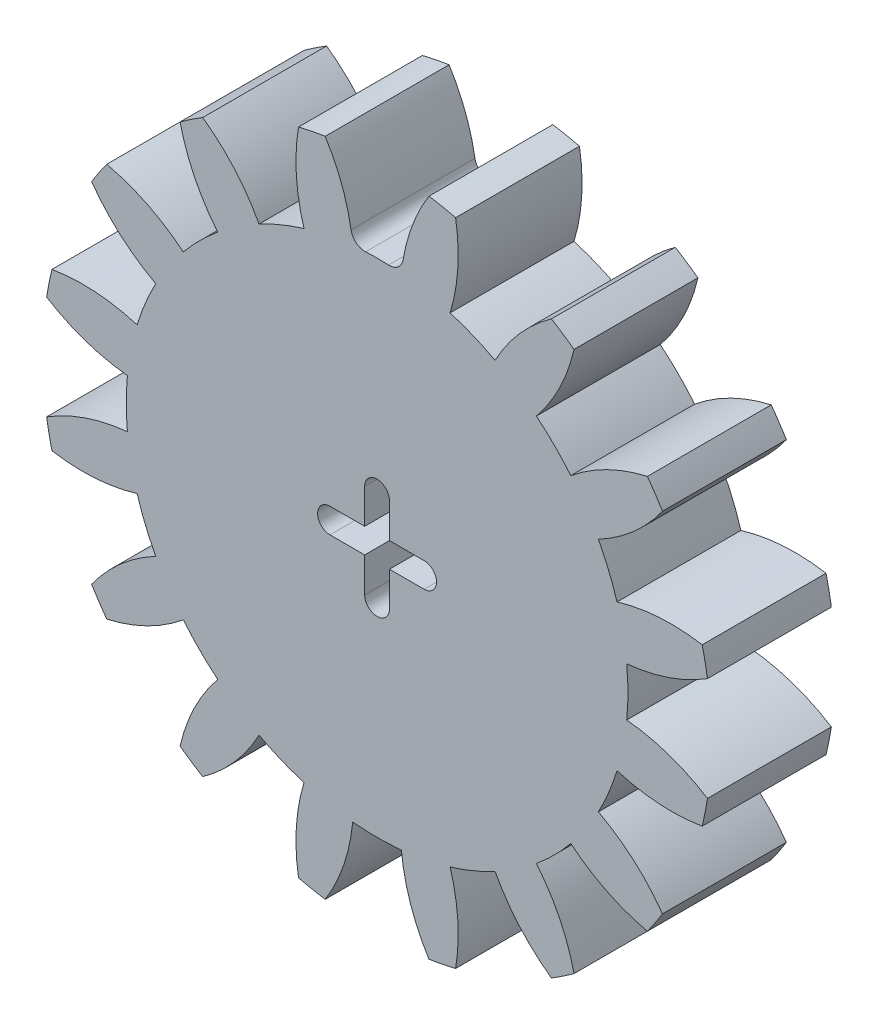
SolidWorks part; units mm, degrees
ref_plane "Front Plane" through (0, 0, 0) normal (0, 0, 1) x (1, 0, 0)
ref_plane "Top Plane" through (0, 0, 0) normal (0, 1, 0) x (1, 0, 0)
ref_plane "Right Plane" through (0, 0, 0) normal (1, 0, 0) x (0, 0, -1)
sketch "Sketch1" plane through (0, 0, 0) normal (0, 0, 1) x (1, 0, 0)
  line L0 (0, -1.9) -> (0, 1.9) construction
  line L1 (-0.5, -1.9) -> (-0.5, 1.9)
  line L2 (0.5, -1.9) -> (0.5, 1.9)
  line L3 (-1.9, 0) -> (1.9, 0) construction
  line L4 (-1.9, 0.5) -> (1.9, 0.5)
  line L5 (-1.9, -0.5) -> (1.9, -0.5)
  circle A0 centre (0, 0) radius 13.5
  arc A2 (-0.5, -1.9) -> (0.5, -1.9) centre (0, -1.9) ccw
  arc A3 (0.5, 1.9) -> (-0.5, 1.9) centre (0, 1.9) ccw
  arc A4 (-1.9, 0.5) -> (-1.9, -0.5) centre (-1.9, 0) ccw
  arc A5 (1.9, -0.5) -> (1.9, 0.5) centre (1.9, 0) ccw
  point P5 (0, 0)
  point P11 (0, 0)
  dimension "D2" = 27
  dimension "D1" = 4.8
  dimension "D3" = 4.8
  dimension "D4" = 1
  dimension "D5" = 1
extrude "Boss-Extrude1" add sketch "Sketch1" along normal mid plane 5 contours A0 A5 L5 L2 A2 L1 A4 L4 A3 region at (-13.1182, 0, 0)
sketch "Sketch2" plane through (0, 0, 0) normal (0, 0, 1) x (1, 0, 0)
  line L0 (0, 0) -> (0, 13.5) construction
  line L1 (0, 0) -> (-0.9822, 10.0772) construction
  line L2 (0, 8.0719) -> (-4.2467, 19.7397) construction
  arc A0 (1.3999, 11.9181) -> (-1.3999, 11.9181) centre (0, 0) ccw construction
  arc A1 (0.9822, 10.0772) -> (-0.9822, 10.0772) centre (0, 0) ccw
  arc A3 (2.0928, 13.3368) -> (-2.0928, 13.3368) centre (0, 0) ccw
  arc A4 (-0.9822, 10.0772) -> (-2.0928, 13.3368) centre (-8.4601, 9.3484) ccw
  arc A5 (0.9822, 10.0772) -> (2.0928, 13.3368) centre (8.4601, 9.3484) cw
  circle A6 centre (0, 0) radius 13.5 construction
  point P16 (0, 0)
  point P17 (0, 0)
  point P18 (0, 0)
  point P19 (0, 0.6134)
  point P20 (0, 0)
  point P21 (0, 0)
  dimension "D1" = 24
  dimension "D2" = 3.375
  dimension "D3" = 20
  dimension "D4" = 2.8062
extrude "Cut-Extrude1" cut sketch "Sketch2" against normal through all both and the other way through all
fillet "Fillet1" radius 0.57 2 edges at (0.9822, 10.0772, 0) (-0.9822, 10.0772, 0)
pattern_circular "CirPattern3" count 16 over 360 about axis through (0, 0, 2.5) along (0, 0, -1) of "Cut-Extrude1"
equation "\"Module\"= 1.5"
equation "\"Pressure Angle\"= 20"
equation "\"Bore\"= 2"
equation "\"NumTeeth\"= 16"
equation "\"D2@Sketch1\"=(\"NumTeeth\"+2)*\"Module\""
equation "\"D1@Sketch2\"=\"NumTeeth\"*\"Module\""
equation "\"ToothDepth\"= IIF ( \"Module\" < 1.25 , 2.4 * \"Module\" , 2.25 * \"Module\" )"
equation "\"D2@Sketch2\"=\"ToothDepth\""
equation "\"D3@Sketch2\"=\"Pressure Angle\""
equation "\"D4@Sketch2\"=((\"Module\"*PI)/2)+0.3*\"Module\""
equation "\"D1@Fillet1\"=\"Module\"*0.38"
equation "\"D1@CirPattern3\"=\"NumTeeth\""
equation "\"D3@Sketch1\"=\"D1@Sketch1\""
equation "\"D5@Sketch1\"=\"D4@Sketch1\""
